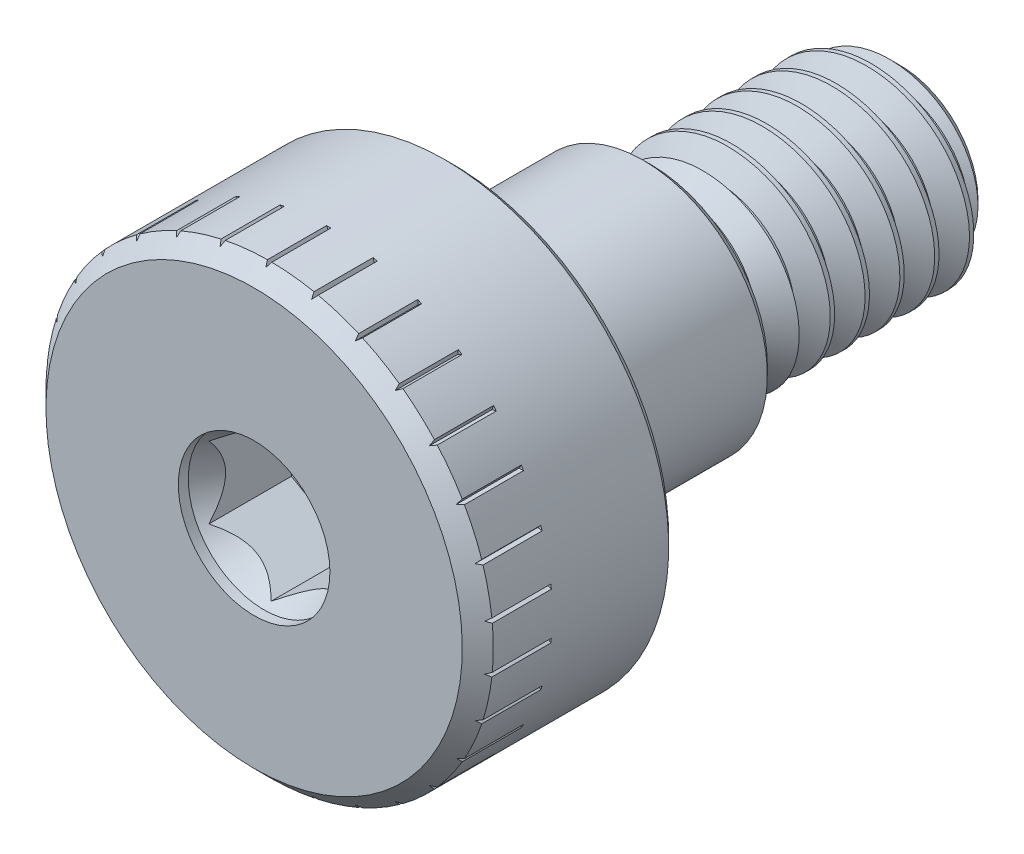
SolidWorks part; units mm, degrees
ref_plane "Front Plane" through (0, 0, 0) normal (0, 0, 1) x (1, 0, 0)
ref_plane "Top Plane" through (0, 0, 0) normal (0, 1, 0) x (1, 0, 0)
ref_plane "Right Plane" through (0, 0, 0) normal (1, 0, 0) x (0, 0, -1)
sketch "Sketch1" plane through (0, 0, 0) normal (1, 0, 0) x (0, 0, -1)
  line L0 (-6.5, 0) -> (6.5, 0) construction
  line L1 (-6.5, -4.5) -> (-6.5, 4.5)
  line L2 (-2.5, -4.5) -> (-2.5, 4.5)
  line L3 (1.5, 2.5) -> (1.5, -2.5)
  line L4 (-6.5, 1.25) -> (-6.5, -1.25)
  line L5 (6.5, 2) -> (6.5, -2)
  line L6 (6.4562, 2.0758) -> (7.1562, 2.0758) construction
  line L7 (7.1562, 2.0758) -> (6.8062, 1.4696) construction
  line L8 (6.8062, 1.4696) -> (6.4562, 2.0758) construction
  line L9 (6.8062, 2.0758) -> (6.8062, 2) construction
  line L10 (6.8062, 1.4696) -> (6.8062, 1.5453) construction
  line L11 (6.5, 2) -> (7.1125, 2) construction
  line L12 (6.4781, 2.0379) -> (7.1344, 2.0379) construction
  line L13 (6.7625, 1.5453) -> (6.85, 1.5453) construction
  line L14 (-2.5, 0) -> (-2.1, 0) construction
  line L15 (-2.1, 0) -> (1.1, 0) construction
  line L16 (1.1, 0) -> (1.5, 0) construction
  point P0 (4.05, -2)
  point P4 (0, 0)
  point P8 (-6.5, 0)
  point P11 (-2.5, 0)
  point P14 (1.5, 0)
  point P17 (-6.5, 0)
  point P20 (6.5, 0)
  point P28 (6.8062, 2)
  point P32 (6.8062, 2.0379)
  point P35 (6.8062, 1.5453)
  point P36 (6.5, 2.5)
  dimension "D1" = 2.45
  dimension "D3" = 0.0875
  dimension "D2" = 3.2
sketch "Sketch2" plane through (0, 0, 0) normal (1, 0, 0) x (0, 0, -1)
  line L0 (6.5, 0) -> (6.5, 1.5625)
  line L2 (6.5, 1.5625) -> (6.0625, 2)
  line L3 (6.0625, 2) -> (2.532, 2)
  line L4 (2.532, 2) -> (2.0773, 1.5453)
  line L5 (2.0773, 1.5453) -> (1.7273, 1.5453)
  line L6 (6.8062, 1.4696) -> (6.4562, 2.0758) construction
  line L7 (1.5, 1.7727) -> (1.5, 2.325)
  line L8 (1.325, 2.5) -> (-1.4368, 2.5)
  line L9 (-1.4368, 2.5) -> (-1.7888, 2.2968)
  line L10 (-1.7888, 2.2968) -> (-1.8777, 2.2968)
  line L11 (-2.5, -4.5) -> (-2.5, 4.5) construction
  line L12 (-6.5, -4.5) -> (-6.5, 4.5) construction
  line L13 (-2.66, 4.5) -> (-6.1876, 4.5)
  line L14 (-6.5, 4.1876) -> (-6.5, 0)
  line L15 (-6.5, 0) -> (6.5, 0)
  line L16 (-6.1876, 4.5) -> (-6.5, 4.1876)
  line L17 (-2.5, 4.34) -> (-2.5, 2.9191)
  line L18 (1.325, 2.5) -> (1.5, 2.325)
  line L19 (1.5, 2.5) -> (1.5, -2.5) construction
  line L20 (-2.66, 4.5) -> (-2.5, 4.34)
  arc A0 (1.7273, 1.5453) -> (1.5, 1.7727) centre (1.7273, 1.7727) cw
  arc A1 (-1.8777, 2.2968) -> (-2.5, 2.9191) centre (-1.8777, 2.9191) cw
  point P23 (6.6312, 1.7727)
  dimension "D4" = 0.35
  dimension "D6" = 30
  dimension "D7" = 0.2032
  dimension "D8" = 0.3124
  dimension "D11" = 0.175
  dimension "D3" = 45
  dimension "D9" = 0.16
  dimension "D10" = 0.0889
  dimension "D5" = 0.7112
  dimension "D2" = 0.4375
revolve "Revolve1" add sketch "Sketch2" angle 360 about L15
sketch "Sketch3" plane through (0, 0, 6.5) normal (0, 0, 1) x (1, 0, 0)
  line L1 (0, 1.4434) -> (-1.25, 0.7217)
  line L2 (-1.25, 0.7217) -> (-1.25, -0.7217)
  line L3 (-1.25, -0.7217) -> (0, -1.4434)
  line L4 (0, -1.4434) -> (1.25, -0.7217)
  line L5 (1.25, -0.7217) -> (1.25, 0.7217)
  line L6 (1.25, 0.7217) -> (0, 1.4434)
  circle A0 centre (0, 0) radius 1.25 construction
  circle A1 centre (0, 0) radius 4.5 construction
  circle A2 centre (0, 0) radius 4.5 construction
extrude "Cut-Extrude1" cut sketch "Sketch3" against normal blind 2
sketch "Sketch4" plane through (0, 0, 6.5) normal (0, 0, 1) x (1, 0, 0)
  circle A0 centre (0, 0) radius 1.525
  dimension "D1" = 3.05
extrude "Cut-Extrude2" cut sketch "Sketch4" against normal blind 0.2
extrude "Cut-Extrude3" cut sketch "Sketch4<2>" against normal blind 1.5 draft 30 from surface starting at face at (1.525, 0, 6.3)
sketch "Sketch4<2>" plane through (0, 0, 6.5) normal (0, 0, 1) x (1, 0, 0) same geometry as "Sketch4"
ref_axis "Center Axis 1" through (0, 0, 15.9563) along (0, 0, -1)
ref_plane "Contact Plane 1" through (0, 0, 2.5) normal (0, 0, -1) x (-1, 0, 0)
sketch "Sketch5" plane through (0, 0, -6.5) normal (0, 0, -1) x (-1, 0, 0)
  circle A0 centre (0, 0) radius 2
curve "Helix/Spiral1" pitch 0.7 height 4.65 radius 2 centre (0, 0, -6.5) axis (0, 0, 1) start towards (0, 1, 0)
sketch "Sketch6" plane through (0, 0, 0) normal (1, 0, 0) x (0, 0, -1)
  line L0 (6.4781, 2.0379) -> (7.1344, 2.0379)
  line L1 (7.1344, 2.0379) -> (6.85, 1.5453)
  line L2 (6.85, 1.5453) -> (6.7625, 1.5453)
  line L3 (6.7625, 1.5453) -> (6.4781, 2.0379)
sweep "Cut-Sweep1" cut profiles "Sketch6" path "Helix/Spiral1"
ref_plane "Plane1" through (0, 0, 5) normal (0, 0, 1) x (1, 0, 0)
sketch "Sketch7" plane through (0, 0, 6.5) normal (0, 0, 1) x (1, 0, 0)
  line L0 (-0.0437, 4.5) -> (0, 4.4242)
  line L1 (0, -4.5) -> (0, 4.5) construction
  line L2 (0, 4.4242) -> (0.0437, 4.5)
  line L3 (0.0437, 4.5) -> (-0.0437, 4.5)
  line L4 (-0.0437, 4.5) -> (0, 0) construction
  line L5 (0, 0) -> (0.0437, 4.5) construction
  dimension "D1" = 0.0875
  dimension "D2" = 1.114
extrude "Cut-Extrude4" cut sketch "Sketch7" against normal up to surface (1.5 mm away) up to plane "Plane1"
pattern_circular "CirPattern1" count 30 over 360 about axis through (0, 0, 6.5) along (0, 0, -1) of "Cut-Extrude4"
ref_axis "Axis1" through (0, 0, -7.8391) along (0, 0, 1)
sketch3d "3DSketch1"
  line L0 (0, 0, 0) -> (0, 0, 6.5)
  line L1 (0, 0, 6.3) -> (0, 0, 6.5) construction
  line L2 (0, 0, 6.1876) -> (0, 0, 6.5) construction
equation "\"D3@Sketch1\" = \"Thread Pitch@Sketch1\" / 8"
equation "\"D1@Sketch1\" = \"Thread Pitch@Sketch1\" * 3.5"
equation "\"D4@Sketch2\" = \"Thread Pitch@Sketch1\" / 2"
equation "\"D8@Sketch2\"=\"Thread Size@Sketch1\" * .0781"
equation "\"D11@Sketch2\"=\"Thread Pitch@Sketch1\" * .25"
equation "\"D1@Cut-Extrude1\" = \"Thread Size@Sketch1\" * .5"
equation "\"D1@Cut-Extrude2\"=\"D1@Cut-Extrude1\" * .1"
equation "\"D4@Helix/Spiral1\" = \"Thread Pitch@Sketch1\""
equation "\"D3@Helix/Spiral1\" = \"Thread Length@Sketch1\" - ( \"Thread Pitch@Sketch1\" / 2 )"
equation "\"D1@Plane1\" = \"Head Height@Sketch1\" * .375"
equation "\"D1@Sketch7\" = \"Thread Pitch@Sketch1\" * .125"
equation "\"D1@CirPattern1\"=( 180 / \"D2@Sketch7\" )  * .1875"
equation "\"D2@Sketch1\"=\"Shoulder Length@Sketch1\"*.80"
equation "\"D1@Sketch4\"=\"Drive Size@Sketch1\" * 1.22"
equation "\"D9@Sketch2\"=\"thread size@sketch1\"*.04"
equation "\"D10@Sketch2\"=\"D5@Sketch2\"*.125"
equation "\"D1@Cut-Extrude3\" = \"D1@Cut-Extrude1\" * .75"
equation "\"D2@Sketch2\"=\"Thread Pitch@Sketch1\"*.625"
